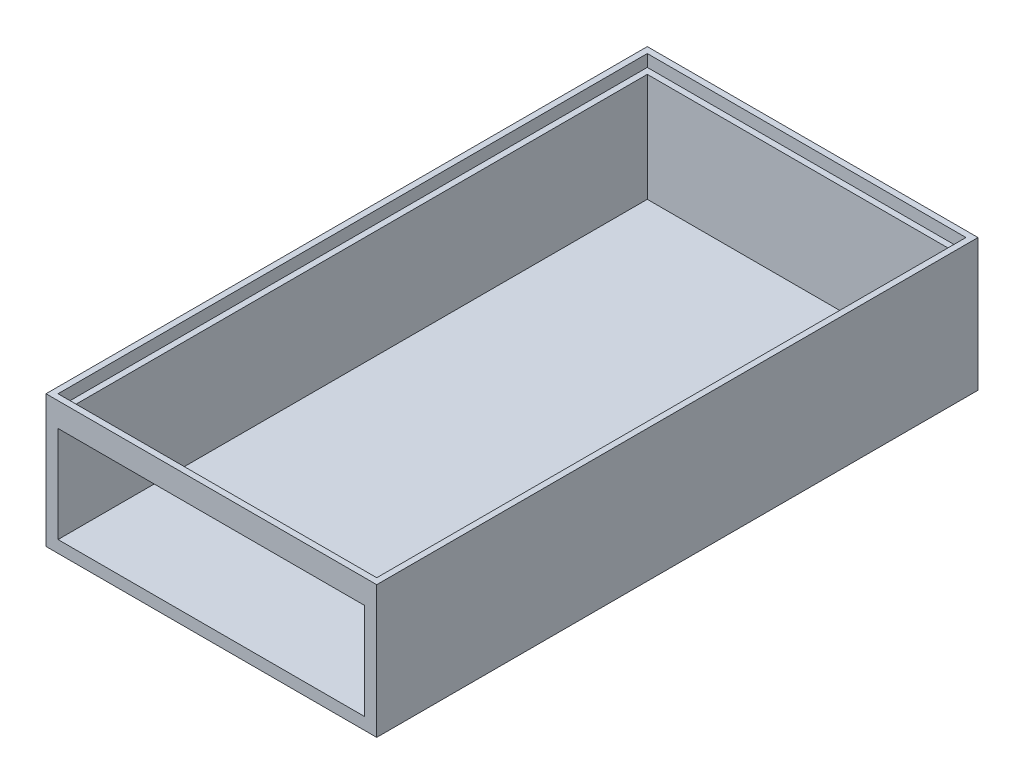
SolidWorks part; units mm, degrees
ref_plane "Front Plane" through (0, 0, 0) normal (0, 0, 1) x (1, 0, 0)
ref_plane "Top Plane" through (0, 0, 0) normal (0, 1, 0) x (1, 0, 0)
ref_plane "Right Plane" through (0, 0, 0) normal (1, 0, 0) x (0, 0, -1)
sketch "Sketch1" plane through (0, 0, 0) normal (0, 1, 0) x (1, 0, 0)
  line L1 (0, 0) -> (139.7, 0)
  line L2 (0, 0) -> (0, 254)
  line L3 (0, 254) -> (139.7, 254)
  line L4 (139.7, 0) -> (139.7, 254)
  dimension "D1" = 254
  dimension "D2" = 139.7
extrude "Boss-Extrude1" add sketch "Sketch1" along normal blind 5.08
sketch "Sketch2" plane through (0, 5.08, 0) normal (0, 1, 0) x (1, 0, 0)
  line L1 (0, 254) -> (139.7, 254)
  line L2 (0, 254) -> (0, 0)
  line L3 (0, 0) -> (139.7, 0)
  line L4 (139.7, 254) -> (139.7, 0)
  line L5 (5.08, 248.92) -> (134.62, 248.92)
  line L6 (5.08, 248.92) -> (5.08, 5.08)
  line L7 (5.08, 5.08) -> (134.62, 5.08)
  line L8 (134.62, 248.92) -> (134.62, 5.08)
  line M9 (0, 254) -> (0, 0)
  line M10 (0, 0) -> (139.7, 0)
  line M11 (139.7, 0) -> (139.7, 254)
  line M12 (139.7, 254) -> (0, 254)
  dimension "D1" = 5.08
  dimension "D2" = 5.08
  dimension "D3" = 5.08
  dimension "D4" = 5.08
extrude "Boss-Extrude2" add sketch "Sketch2" along normal blind 50.8 contours L5 L8 L7 L6 M12 M9 M10 M11 region at (69.85, 5.08, -251.1012)
sketch "Sketch3" plane through (0, 55.88, 0) normal (0, 1, 0) x (1, 0, 0)
  line L1 (5.08, 248.92) -> (134.62, 248.92)
  line L2 (5.08, 248.92) -> (5.08, 5.08)
  line L3 (5.08, 5.08) -> (134.62, 5.08)
  line L4 (134.62, 248.92) -> (134.62, 5.08)
  line L5 (2.54, 251.46) -> (137.16, 251.46)
  line L6 (2.54, 251.46) -> (2.54, 2.54)
  line L7 (2.54, 2.54) -> (137.16, 2.54)
  line L8 (137.16, 251.46) -> (137.16, 2.54)
  line M13 (5.08, 248.92) -> (134.62, 248.92)
  line M14 (134.62, 248.92) -> (134.62, 5.08)
  line M15 (134.62, 5.08) -> (5.08, 5.08)
  line M16 (5.08, 5.08) -> (5.08, 248.92)
  dimension "D1" = 2.54
  dimension "D2" = 2.54
  dimension "D3" = 2.54
  dimension "D4" = 2.54
extrude "Cut-Extrude1" cut sketch "Sketch3" against normal blind 5.08 contours L8 L5 L6 L7 M16 M13 M14 M15 region at (69.85, 55.88, -251.177)
sketch "Sketch4" plane through (0, 0, 0) normal (0, 0, 1) x (1, 0, 0)
  line L0 (0, 0) -> (139.7, 0) construction
  line L1 (5.08, 45.72) -> (134.62, 45.72)
  line L2 (5.08, 45.72) -> (5.08, 5.08)
  line L3 (5.08, 5.08) -> (134.62, 5.08)
  line L4 (134.62, 45.72) -> (134.62, 5.08)
  line L5 (0, 55.88) -> (0, 0) construction
  line L6 (139.7, 55.88) -> (139.7, 0) construction
  line L7 (0, 55.88) -> (139.7, 55.88) construction
  dimension "D1" = 5.08
  dimension "D2" = 5.08
  dimension "D3" = 5.08
  dimension "D4" = 10.16
extrude "Cut-Extrude2" cut sketch "Sketch4" against normal up to next
